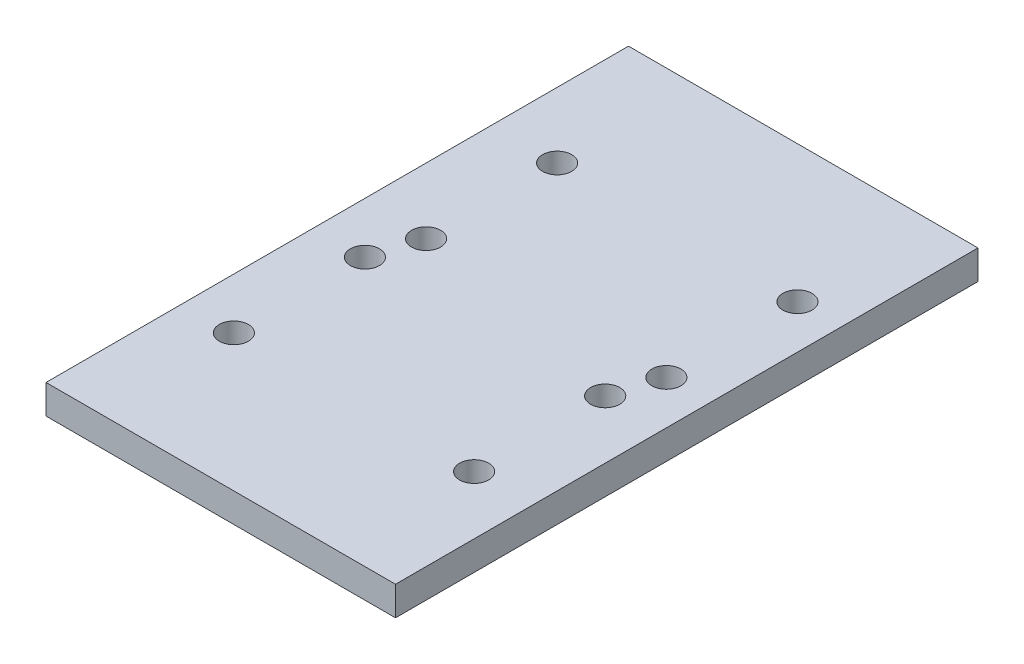
SolidWorks part; units mm, degrees
material "Aleación 6061"
ref_plane "Alzado" through (0, 0, 0) normal (0, 0, 1) x (1, 0, 0)
ref_plane "Planta" through (0, 0, 0) normal (0, 1, 0) x (1, 0, 0)
ref_plane "Vista lateral" through (0, 0, 0) normal (1, 0, 0) x (0, 0, -1)
sketch "Croquis1" plane through (0, 0, 0) normal (0, 0, 1) x (1, 0, 0)
  line L1 (-24, 2) -> (24, 2)
  line L2 (-24, 2) -> (-24, -2)
  line L3 (-24, -2) -> (24, -2)
  line L4 (24, 2) -> (24, -2)
  line L5 (-24, 2) -> (24, -2) construction
  line L6 (-24, -2) -> (24, 2) construction
  point P0 (0, 0)
  dimension "D1" = 4
  dimension "D2" = 48
extrude "Saliente-Extruir1" add sketch "Croquis1" along normal blind 80
sketch "Croquis3" plane through (0, -2, 0) normal (0, -1, 0) x (-1, 0, 0)
  line L0 (24, -80) -> (-24, -80) construction
  line L1 (-24, -80) -> (-24, 0) construction
  line L3 (24, 0) -> (-24, 0) construction
  line L4 (-18, -61.2) -> (-18, -43.2)
  line L5 (-14, -43.2) -> (-14, -61.2)
  line L6 (0.5, -71.4251) -> (0.5, -37.2376) construction
  line L7 (-20, -18.8) -> (-20, -36.8)
  line L8 (-16, -36.8) -> (-16, -18.8)
  line L9 (-1.5, -41.2964) -> (-1.5, -9.7375) construction
  line L10 (15, -43.2) -> (15, -61.2)
  line L11 (19, -61.2) -> (19, -43.2)
  line L12 (13, -36.8) -> (13, -18.8)
  line L13 (17, -18.8) -> (17, -36.8)
  arc A0 (-18, -61.2) -> (-14, -61.2) centre (-16, -61.2) ccw
  arc A1 (-16, -18.8) -> (-20, -18.8) centre (-18, -18.8) ccw
  arc A2 (-18, -43.2) -> (-14, -43.2) centre (-16, -43.2) cw
  arc A3 (-20, -36.8) -> (-16, -36.8) centre (-18, -36.8) ccw
  arc A4 (19, -43.2) -> (15, -43.2) centre (17, -43.2) ccw
  arc A5 (19, -61.2) -> (15, -61.2) centre (17, -61.2) cw
  arc A6 (17, -36.8) -> (13, -36.8) centre (15, -36.8) cw
  arc A7 (13, -18.8) -> (17, -18.8) centre (15, -18.8) cw
  dimension "D3" = 4
  dimension "D4" = 4
  dimension "D7" = 2
  dimension "D11" = 2
  dimension "D1" = 18.8
  dimension "D2" = 8
  dimension "D5" = 6
  dimension "D6" = 18.8
  dimension "D8" = 18
  dimension "D9" = 8
  dimension "D10" = 16.5
  dimension "D12" = 6
  dimension "D13" = 18
  dimension "D14" = 16.5
sketch "Croquis6" plane through (0, -2, 0) normal (0, -1, 0) x (1, 0, 0)
  circle A0 centre (16, 61.2) radius 2
  circle A1 centre (18, 36.8) radius 2
  circle A2 centre (18, 18.8) radius 2
  circle A3 centre (-17, 61.2) radius 2
  circle A4 centre (-15, 36.8) radius 2
  circle A5 centre (-15, 18.8) radius 2
  circle A6 centre (-17, 43.2) radius 2
  circle A7 centre (16, 43.2) radius 2
extrude "Cortar-Extruir4" cut sketch "Croquis6" against normal through all
